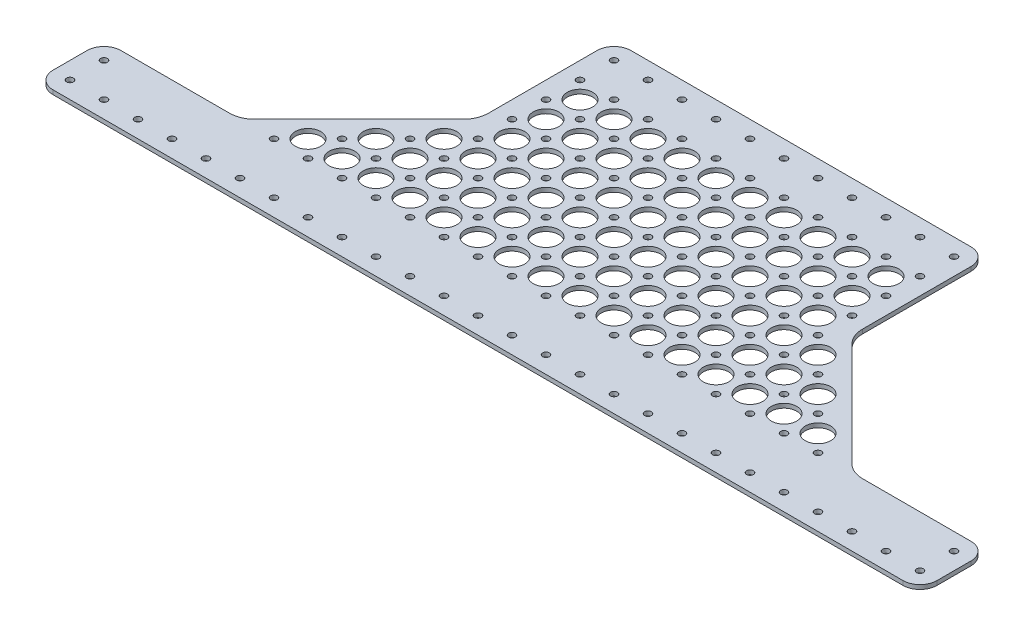
SolidWorks part; units mm, degrees
material "6061 Alloy"
ref_plane "Front Plane" through (0, 0, 0) normal (0, 0, 1) x (1, 0, 0)
ref_plane "Top Plane" through (0, 0, 0) normal (0, 1, 0) x (1, 0, 0)
ref_plane "Right Plane" through (0, 0, 0) normal (1, 0, 0) x (0, 0, -1)
sketch "Sketch1" plane through (0, 0, 0) normal (0, 1, 0) x (1, 0, 0)
  line L0 (0, 0) -> (0, 101.6)
  line L1 (0, 101.6) -> (279.4, 101.6)
  line L2 (279.4, 101.6) -> (279.4, 0)
  line L3 (279.4, 0) -> (368.3045, -88.9045)
  line L4 (368.3045, -88.9045) -> (469.9045, -88.9045)
  line L5 (469.9045, -88.9045) -> (469.9045, -419.1045)
  line L6 (469.9045, -419.1045) -> (368.3045, -419.1045)
  line L7 (368.3045, -419.1045) -> (279.4, -508.0091)
  line L8 (279.4, -508.0091) -> (279.4, -609.6091)
  line L9 (279.4, -609.6091) -> (0, -609.6091)
  line L10 (0, -609.6091) -> (0, -508.0091)
  line L11 (0, -508.0091) -> (-88.9045, -419.1045)
  line L12 (-88.9045, -419.1045) -> (-190.5045, -419.1045)
  line L13 (-190.5045, -419.1045) -> (-190.5045, -88.9045)
  line L14 (-190.5045, -88.9045) -> (-88.9045, -88.9045)
  line L15 (-88.9045, -88.9045) -> (0, 0)
  line L16 (-190.5045, -88.9045) -> (-177.8045, -88.9045)
  line L17 (-177.8045, -88.9045) -> (-177.8045, -419.1045) construction
  line L18 (-177.8045, -419.1045) -> (-190.5045, -419.1045)
  line L19 (-177.8045, -101.6045) -> (-177.8045, -127.0045) construction
  line L20 (139.7, -898.4) -> (139.7, 49101.6) construction
  line L21 (-966.4523, 88.9) -> (49033.5477, 88.9) construction
  line L22 (12.7, 88.9) -> (38.1, 88.9) construction
  line L23 (-1190.5045, -254.0045) -> (48809.4955, -254.0045) construction
  line L24 (-190.5045, -368.3045) -> (-88.9045, -368.3045) construction
  line L25 (-88.9045, -368.3045) -> (-88.9045, -419.1045) construction
  line L26 (-101.6045, -406.4045) -> (-127.0045, -406.4045) construction
  line L27 (-101.6045, -381.0045) -> (-127.0045, -381.0045) construction
  line L28 (-1102.5698, -114.3045) -> (48897.4302, -114.3045) construction
  line L29 (-1089.6596, -165.1045) -> (48910.3404, -165.1045) construction
  line L30 (-177.8045, -127.0045) -> (-152.4045, -127.0045) construction
  circle A0 centre (-177.8045, -101.6045) radius 2.54
  circle A1 centre (-177.8045, -127.0045) radius 2.54
  circle A2 centre (-177.8045, -152.4045) radius 2.54
  circle A3 centre (-177.8045, -177.8045) radius 2.54
  circle A4 centre (-177.8045, -203.2045) radius 2.54
  circle A5 centre (-177.8045, -228.6045) radius 2.54
  circle A6 centre (-177.8045, -254.0045) radius 2.54
  circle A7 centre (-177.8045, -279.4045) radius 2.54
  circle A8 centre (-177.8045, -304.8045) radius 2.54
  circle A9 centre (-177.8045, -330.2045) radius 2.54
  circle A10 centre (-177.8045, -355.6045) radius 2.54
  circle A11 centre (-177.8045, -381.0045) radius 2.54
  circle A12 centre (-177.8045, -406.4045) radius 2.54
  circle A13 centre (457.2045, -406.4045) radius 2.54
  circle A14 centre (457.2045, -381.0045) radius 2.54
  circle A15 centre (457.2045, -355.6045) radius 2.54
  circle A16 centre (457.2045, -330.2045) radius 2.54
  circle A17 centre (457.2045, -304.8045) radius 2.54
  circle A18 centre (457.2045, -279.4045) radius 2.54
  circle A19 centre (457.2045, -254.0045) radius 2.54
  circle A20 centre (457.2045, -228.6045) radius 2.54
  circle A21 centre (457.2045, -152.4045) radius 2.54
  circle A22 centre (457.2045, -177.8045) radius 2.54
  circle A23 centre (457.2045, -203.2045) radius 2.54
  circle A24 centre (457.2045, -127.0045) radius 2.54
  circle A25 centre (457.2045, -101.6045) radius 2.54
  circle A26 centre (12.7, 88.9) radius 2.54
  circle A27 centre (38.1, 88.9) radius 2.54
  circle A28 centre (63.5, 88.9) radius 2.54
  circle A29 centre (88.9, 88.9) radius 2.54
  circle A30 centre (114.3, 88.9) radius 2.54
  circle A31 centre (139.7, 88.9) radius 2.54
  circle A32 centre (165.1, 88.9) radius 2.54
  circle A33 centre (190.5, 88.9) radius 2.54
  circle A34 centre (215.9, 88.9) radius 2.54
  circle A35 centre (241.3, 88.9) radius 2.54
  circle A36 centre (266.7, 88.9) radius 2.54
  circle A37 centre (266.7, -596.9091) radius 2.54
  circle A38 centre (241.3, -596.9091) radius 2.54
  circle A39 centre (215.9, -596.9091) radius 2.54
  circle A40 centre (190.5, -596.9091) radius 2.54
  circle A41 centre (165.1, -596.9091) radius 2.54
  circle A42 centre (139.7, -596.9091) radius 2.54
  circle A43 centre (114.3, -596.9091) radius 2.54
  circle A44 centre (88.9, -596.9091) radius 2.54
  circle A45 centre (63.5, -596.9091) radius 2.54
  circle A46 centre (38.1, -596.9091) radius 2.54
  circle A47 centre (12.7, -596.9091) radius 2.54
  circle A48 centre (-101.6045, -381.0045) radius 2.54
  circle A49 centre (-101.6045, -406.4045) radius 2.54
  circle A50 centre (381.0045, -406.4045) radius 2.54
  circle A51 centre (381.0045, -381.0045) radius 2.54
  circle A52 centre (-127.0045, -406.4045) radius 2.54
  circle A53 centre (-152.4045, -406.4045) radius 2.54
  circle A54 centre (-127.0045, -381.0045) radius 2.54
  circle A55 centre (-152.4045, -381.0045) radius 2.54
  circle A56 centre (431.8045, -381.0045) radius 2.54
  circle A57 centre (406.4045, -381.0045) radius 2.54
  circle A58 centre (431.8045, -406.4045) radius 2.54
  circle A59 centre (406.4045, -406.4045) radius 2.54
  circle A60 centre (-152.4045, -127.0045) radius 2.54
  circle A61 centre (-152.4045, -152.4045) radius 2.54
  circle A62 centre (-127.0045, -127.0045) radius 2.54
  circle A63 centre (-127.0045, -152.4045) radius 2.54
  circle A64 centre (-101.6045, -127.0045) radius 2.54
  circle A65 centre (-101.6045, -152.4045) radius 2.54
  circle A66 centre (-76.2045, -127.0045) radius 2.54
  circle A67 centre (-76.2045, -152.4045) radius 2.54
  circle A68 centre (-50.8045, -127.0045) radius 2.54
  circle A69 centre (-50.8045, -152.4045) radius 2.54
  circle A70 centre (-25.4045, -127.0045) radius 2.54
  circle A71 centre (-25.4045, -152.4045) radius 2.54
  circle A72 centre (-0.0045, -127.0045) radius 2.54
  circle A73 centre (-0.0045, -152.4045) radius 2.54
  circle A74 centre (25.3955, -127.0045) radius 2.54
  circle A75 centre (25.3955, -152.4045) radius 2.54
  circle A76 centre (50.7955, -127.0045) radius 2.54
  circle A77 centre (50.7955, -152.4045) radius 2.54
  circle A78 centre (76.1955, -127.0045) radius 2.54
  circle A79 centre (76.1955, -152.4045) radius 2.54
  circle A80 centre (101.5955, -127.0045) radius 2.54
  circle A81 centre (101.5955, -152.4045) radius 2.54
  circle A82 centre (126.9955, -127.0045) radius 2.54
  circle A83 centre (126.9955, -152.4045) radius 2.54
  circle A84 centre (152.3955, -127.0045) radius 2.54
  circle A85 centre (152.3955, -152.4045) radius 2.54
  circle A86 centre (177.7955, -127.0045) radius 2.54
  circle A87 centre (177.7955, -152.4045) radius 2.54
  circle A88 centre (203.1955, -127.0045) radius 2.54
  circle A89 centre (203.1955, -152.4045) radius 2.54
  circle A90 centre (228.5955, -127.0045) radius 2.54
  circle A91 centre (228.5955, -152.4045) radius 2.54
  circle A92 centre (253.9955, -127.0045) radius 2.54
  circle A93 centre (253.9955, -152.4045) radius 2.54
  circle A94 centre (279.3955, -127.0045) radius 2.54
  circle A95 centre (279.3955, -152.4045) radius 2.54
  circle A96 centre (304.7955, -127.0045) radius 2.54
  circle A97 centre (304.7955, -152.4045) radius 2.54
  circle A98 centre (330.1955, -127.0045) radius 2.54
  circle A99 centre (330.1955, -152.4045) radius 2.54
  circle A100 centre (355.5955, -127.0045) radius 2.54
  circle A101 centre (355.5955, -152.4045) radius 2.54
  circle A102 centre (380.9955, -127.0045) radius 2.54
  circle A103 centre (380.9955, -152.4045) radius 2.54
  circle A104 centre (406.3955, -127.0045) radius 2.54
  circle A105 centre (406.3955, -152.4045) radius 2.54
  circle A106 centre (431.7955, -127.0045) radius 2.54
  circle A107 centre (431.7955, -152.4045) radius 2.54
  point P50 (139.7, 101.6)
  point P105 (-190.5045, -254.0045)
  dimension "D11" = 5.08
  dimension "D16" = 5.08
  dimension "D21" = 5.08
  dimension "D22" = 5.08
  dimension "D1" = 135
  dimension "D2" = 135
  dimension "D3" = 135
  dimension "D4" = 135
  dimension "D5" = 101.6
  dimension "D6" = 279.4
  dimension "D7" = 330.2
  dimension "D8" = 101.6
  dimension "D9" = 125.73
  dimension "D10" = 12.7
  dimension "D12" = 12.7
  dimension "D13" = 25.4
  dimension "D15" = 12.7
  dimension "D17" = 12.7
  dimension "D18" = 25.4
  dimension "D19" = 101.6
  dimension "D20" = 50.8
  dimension "D23" = 12.7
  dimension "D24" = 12.7
  dimension "D25" = 12.7
  dimension "D26" = 12.7
  dimension "D27" = 25.4
  dimension "D28" = 25.4
  dimension "D29" = 25.4
  dimension "D30" = 50.8
  dimension "D31" = 25.4
  dimension "D14" = 13
extrude "Boss-Extrude1" add sketch "Sketch1" along normal blind 3.175 contours L15 L14 L13 L12 L11 L10 L9 L8 L7 L6 L5 L4 L3 L2 L1 L0 A107 A106 A105 A104 A103 A102 A101 A100 A99 A98 A97 A96 A95 A94 A93 A92 region at (139.7, 0, 254.2329)
sketch "Sketch2" plane through (0, 0, 609.6091) normal (0, 0, 1) x (1, 0, 0)
  line L0 (279.4, 0) -> (0, 0) construction
  line L1 (-203.0133, -12.7) -> (508.1867, -12.7)
  line L2 (-203.0133, -12.7) -> (-203.0133, 12.7)
  line L3 (-203.0133, 12.7) -> (508.1867, 12.7)
  line L4 (508.1867, -12.7) -> (508.1867, 12.7)
  line L5 (-203.0133, -12.7) -> (508.1867, 12.7) construction
  line L6 (-203.0133, 12.7) -> (508.1867, -12.7) construction
  point P0 (152.5867, 0)
  dimension "D1" = 711.2
  dimension "D2" = 25.4
extrude "Cut-Extrude2" cut sketch "Sketch2" against normal blind 469.9
sketch "Sketch3" plane through (0, 3.175, 0) normal (0, 1, 0) x (1, 0, 0)
  line L0 (12.7, 88.9) -> (38.1, 88.9) construction
  line L1 (12.7, 88.9) -> (12.7, 63.5) construction
  line L2 (0, 0) -> (0, 101.6) construction
  line L3 (12.7, -88.9) -> (-12.7, -88.9) construction
  line L4 (12.7, -63.5) -> (-12.7, -63.5) construction
  line L5 (12.7, -38.1) -> (-12.7, -38.1) construction
  line L6 (0, 101.6) -> (279.4, 101.6) construction
  line L7 (266.7, -88.9) -> (292.1, -88.9) construction
  line L8 (266.7, -63.5) -> (292.1, -63.5) construction
  line L9 (266.7, -38.1) -> (292.1, -38.1) construction
  line L10 (25.4, 50.8) -> (50.8, 50.8) construction
  line L11 (25.4, 50.8) -> (25.4, 25.4) construction
  line L12 (279.4, 101.6) -> (279.4, 0) construction
  line L13 (25.4, -25.4) -> (0, -25.4) construction
  circle A0 centre (12.7, 88.9) radius 2.54
  circle A1 centre (38.1, 88.9) radius 2.54
  circle A2 centre (63.5, 88.9) radius 2.54
  circle A3 centre (88.9, 88.9) radius 2.54
  circle A4 centre (114.3, 88.9) radius 2.54
  circle A5 centre (139.7, 88.9) radius 2.54
  circle A6 centre (165.1, 88.9) radius 2.54
  circle A7 centre (190.5, 88.9) radius 2.54
  circle A8 centre (215.9, 88.9) radius 2.54
  circle A9 centre (241.3, 88.9) radius 2.54
  circle A10 centre (266.7, 88.9) radius 2.54
  circle A18 centre (12.7, 63.5) radius 2.54
  circle A19 centre (38.1, 63.5) radius 2.54
  circle A20 centre (63.5, 63.5) radius 2.54
  circle A21 centre (88.9, 63.5) radius 2.54
  circle A22 centre (114.3, 63.5) radius 2.54
  circle A23 centre (139.7, 63.5) radius 2.54
  circle A24 centre (165.1, 63.5) radius 2.54
  circle A25 centre (190.5, 63.5) radius 2.54
  circle A26 centre (215.9, 63.5) radius 2.54
  circle A27 centre (241.3, 63.5) radius 2.54
  circle A28 centre (266.7, 63.5) radius 2.54
  circle A36 centre (12.7, 38.1) radius 2.54
  circle A37 centre (38.1, 38.1) radius 2.54
  circle A38 centre (63.5, 38.1) radius 2.54
  circle A39 centre (88.9, 38.1) radius 2.54
  circle A40 centre (114.3, 38.1) radius 2.54
  circle A41 centre (139.7, 38.1) radius 2.54
  circle A42 centre (165.1, 38.1) radius 2.54
  circle A43 centre (190.5, 38.1) radius 2.54
  circle A44 centre (215.9, 38.1) radius 2.54
  circle A45 centre (241.3, 38.1) radius 2.54
  circle A46 centre (266.7, 38.1) radius 2.54
  circle A54 centre (12.7, 12.7) radius 2.54
  circle A55 centre (38.1, 12.7) radius 2.54
  circle A56 centre (63.5, 12.7) radius 2.54
  circle A57 centre (88.9, 12.7) radius 2.54
  circle A58 centre (114.3, 12.7) radius 2.54
  circle A59 centre (139.7, 12.7) radius 2.54
  circle A60 centre (165.1, 12.7) radius 2.54
  circle A61 centre (190.5, 12.7) radius 2.54
  circle A62 centre (215.9, 12.7) radius 2.54
  circle A63 centre (241.3, 12.7) radius 2.54
  circle A64 centre (266.7, 12.7) radius 2.54
  circle A72 centre (12.7, -12.7) radius 2.54
  circle A73 centre (38.1, -12.7) radius 2.54
  circle A74 centre (63.5, -12.7) radius 2.54
  circle A75 centre (88.9, -12.7) radius 2.54
  circle A76 centre (114.3, -12.7) radius 2.54
  circle A77 centre (139.7, -12.7) radius 2.54
  circle A78 centre (165.1, -12.7) radius 2.54
  circle A79 centre (190.5, -12.7) radius 2.54
  circle A80 centre (215.9, -12.7) radius 2.54
  circle A81 centre (241.3, -12.7) radius 2.54
  circle A82 centre (266.7, -12.7) radius 2.54
  circle A90 centre (12.7, -38.1) radius 2.54
  circle A91 centre (38.1, -38.1) radius 2.54
  circle A92 centre (63.5, -38.1) radius 2.54
  circle A93 centre (88.9, -38.1) radius 2.54
  circle A94 centre (114.3, -38.1) radius 2.54
  circle A95 centre (139.7, -38.1) radius 2.54
  circle A96 centre (165.1, -38.1) radius 2.54
  circle A97 centre (190.5, -38.1) radius 2.54
  circle A98 centre (215.9, -38.1) radius 2.54
  circle A99 centre (241.3, -38.1) radius 2.54
  circle A100 centre (266.7, -38.1) radius 2.54
  circle A108 centre (12.7, -63.5) radius 2.54
  circle A109 centre (38.1, -63.5) radius 2.54
  circle A110 centre (63.5, -63.5) radius 2.54
  circle A111 centre (88.9, -63.5) radius 2.54
  circle A112 centre (114.3, -63.5) radius 2.54
  circle A113 centre (139.7, -63.5) radius 2.54
  circle A114 centre (165.1, -63.5) radius 2.54
  circle A115 centre (190.5, -63.5) radius 2.54
  circle A116 centre (215.9, -63.5) radius 2.54
  circle A117 centre (241.3, -63.5) radius 2.54
  circle A118 centre (266.7, -63.5) radius 2.54
  circle A126 centre (12.7, -88.9) radius 2.54
  circle A127 centre (38.1, -88.9) radius 2.54
  circle A128 centre (63.5, -88.9) radius 2.54
  circle A129 centre (88.9, -88.9) radius 2.54
  circle A130 centre (114.3, -88.9) radius 2.54
  circle A131 centre (139.7, -88.9) radius 2.54
  circle A132 centre (165.1, -88.9) radius 2.54
  circle A133 centre (190.5, -88.9) radius 2.54
  circle A134 centre (215.9, -88.9) radius 2.54
  circle A135 centre (241.3, -88.9) radius 2.54
  circle A136 centre (266.7, -88.9) radius 2.54
  circle A211 centre (-12.7, -88.9) radius 2.54
  circle A212 centre (-38.1, -88.9) radius 2.54
  circle A213 centre (-63.5, -88.9) radius 2.54
  circle A214 centre (-12.7, -63.5) radius 2.54
  circle A215 centre (-38.1, -63.5) radius 2.54
  circle A216 centre (-12.7, -38.1) radius 2.54
  circle A224 centre (292.1, -88.9) radius 2.54
  circle A225 centre (317.5, -88.9) radius 2.54
  circle A226 centre (342.9, -88.9) radius 2.54
  circle A227 centre (292.1, -63.5) radius 2.54
  circle A228 centre (317.5, -63.5) radius 2.54
  circle A229 centre (292.1, -38.1) radius 2.54
  circle A230 centre (25.4, 50.8) radius 9.525
  circle A231 centre (50.8, 50.8) radius 9.525
  circle A232 centre (292.1, 88.9) radius 2.54 [skipped]
  circle A233 centre (317.5, 88.9) radius 2.54 [skipped]
  circle A234 centre (342.9, 88.9) radius 2.54 [skipped]
  circle A235 centre (368.3, 88.9) radius 2.54 [skipped]
  circle A236 centre (393.7, 88.9) radius 2.54 [skipped]
  circle A237 centre (419.1, 88.9) radius 2.54 [skipped]
  circle A238 centre (444.5, 88.9) radius 2.54 [skipped]
  circle A239 centre (12.7, -114.3) radius 2.54 [skipped]
  circle A240 centre (38.1, -114.3) radius 2.54 [skipped]
  circle A241 centre (63.5, -114.3) radius 2.54 [skipped]
  circle A242 centre (88.9, -114.3) radius 2.54 [skipped]
  circle A243 centre (114.3, -114.3) radius 2.54 [skipped]
  circle A244 centre (139.7, -114.3) radius 2.54 [skipped]
  circle A245 centre (165.1, -114.3) radius 2.54 [skipped]
  circle A246 centre (190.5, -114.3) radius 2.54 [skipped]
  circle A247 centre (215.9, -114.3) radius 2.54 [skipped]
  circle A248 centre (241.3, -114.3) radius 2.54 [skipped]
  circle A249 centre (266.7, -114.3) radius 2.54 [skipped]
  circle A250 centre (76.2, 50.8) radius 9.525
  circle A251 centre (101.6, 50.8) radius 9.525
  circle A252 centre (127, 50.8) radius 9.525
  circle A253 centre (152.4, 50.8) radius 9.525
  circle A254 centre (177.8, 50.8) radius 9.525
  circle A255 centre (203.2, 50.8) radius 9.525
  circle A256 centre (228.6, 50.8) radius 9.525
  circle A257 centre (254, 50.8) radius 9.525
  circle A265 centre (50.8, 25.4) radius 9.525
  circle A266 centre (76.2, 25.4) radius 9.525
  circle A267 centre (101.6, 25.4) radius 9.525
  circle A268 centre (127, 25.4) radius 9.525
  circle A269 centre (152.4, 25.4) radius 9.525
  circle A270 centre (177.8, 25.4) radius 9.525
  circle A271 centre (203.2, 25.4) radius 9.525
  circle A272 centre (228.6, 25.4) radius 9.525
  circle A273 centre (254, 25.4) radius 9.525
  circle A281 centre (50.8, 0) radius 9.525
  circle A282 centre (76.2, 0) radius 9.525
  circle A283 centre (101.6, 0) radius 9.525
  circle A284 centre (127, 0) radius 9.525
  circle A285 centre (152.4, 0) radius 9.525
  circle A286 centre (177.8, 0) radius 9.525
  circle A287 centre (203.2, 0) radius 9.525
  circle A288 centre (228.6, 0) radius 9.525
  circle A289 centre (254, 0) radius 9.525
  circle A297 centre (50.8, -25.4) radius 9.525
  circle A298 centre (76.2, -25.4) radius 9.525
  circle A299 centre (101.6, -25.4) radius 9.525
  circle A300 centre (127, -25.4) radius 9.525
  circle A301 centre (152.4, -25.4) radius 9.525
  circle A302 centre (177.8, -25.4) radius 9.525
  circle A303 centre (203.2, -25.4) radius 9.525
  circle A304 centre (228.6, -25.4) radius 9.525
  circle A305 centre (254, -25.4) radius 9.525
  circle A306 centre (279.4, -25.4) radius 9.525
  circle A313 centre (50.8, -50.8) radius 9.525
  circle A314 centre (76.2, -50.8) radius 9.525
  circle A315 centre (101.6, -50.8) radius 9.525
  circle A316 centre (127, -50.8) radius 9.525
  circle A317 centre (152.4, -50.8) radius 9.525
  circle A318 centre (177.8, -50.8) radius 9.525
  circle A319 centre (203.2, -50.8) radius 9.525
  circle A320 centre (228.6, -50.8) radius 9.525
  circle A321 centre (254, -50.8) radius 9.525
  circle A322 centre (279.4, -50.8) radius 9.525
  circle A323 centre (304.8, -50.8) radius 9.525
  circle A329 centre (50.8, -76.2) radius 9.525
  circle A330 centre (76.2, -76.2) radius 9.525
  circle A331 centre (101.6, -76.2) radius 9.525
  circle A332 centre (127, -76.2) radius 9.525
  circle A333 centre (152.4, -76.2) radius 9.525
  circle A334 centre (177.8, -76.2) radius 9.525
  circle A335 centre (203.2, -76.2) radius 9.525
  circle A336 centre (228.6, -76.2) radius 9.525
  circle A337 centre (254, -76.2) radius 9.525
  circle A338 centre (279.4, -76.2) radius 9.525
  circle A339 centre (304.8, -76.2) radius 9.525
  circle A340 centre (330.2, -76.2) radius 9.525
  circle A345 centre (25.4, 25.4) radius 9.525
  circle A346 centre (25.4, 0) radius 9.525
  circle A347 centre (25.4, -25.4) radius 9.525
  circle A348 centre (25.4, -50.8) radius 9.525
  circle A349 centre (25.4, -76.2) radius 9.525
  circle A350 centre (279.4, 25.4) radius 9.525 [skipped]
  circle A351 centre (304.8, 25.4) radius 9.525 [skipped]
  circle A352 centre (330.2, 25.4) radius 9.525 [skipped]
  circle A353 centre (355.6, 25.4) radius 9.525 [skipped]
  circle A354 centre (381, 25.4) radius 9.525 [skipped]
  circle A355 centre (406.4, 25.4) radius 9.525 [skipped]
  circle A356 centre (431.8, 25.4) radius 9.525 [skipped]
  circle A357 centre (279.4, 0) radius 9.525 [skipped]
  circle A358 centre (304.8, 0) radius 9.525 [skipped]
  circle A359 centre (330.2, 0) radius 9.525 [skipped]
  circle A360 centre (355.6, 0) radius 9.525 [skipped]
  circle A361 centre (381, 0) radius 9.525 [skipped]
  circle A362 centre (406.4, 0) radius 9.525 [skipped]
  circle A363 centre (431.8, 0) radius 9.525 [skipped]
  circle A364 centre (304.8, 50.8) radius 9.525 [skipped]
  circle A365 centre (330.2, 50.8) radius 9.525 [skipped]
  circle A366 centre (355.6, 50.8) radius 9.525 [skipped]
  circle A367 centre (381, 50.8) radius 9.525 [skipped]
  circle A368 centre (406.4, 50.8) radius 9.525 [skipped]
  circle A369 centre (431.8, 50.8) radius 9.525 [skipped]
  circle A370 centre (279.4, 50.8) radius 9.525 [skipped]
  circle A371 centre (330.2, -25.4) radius 9.525 [skipped]
  circle A372 centre (355.6, -25.4) radius 9.525 [skipped]
  circle A373 centre (381, -25.4) radius 9.525 [skipped]
  circle A374 centre (406.4, -25.4) radius 9.525 [skipped]
  circle A375 centre (431.8, -25.4) radius 9.525 [skipped]
  circle A376 centre (381, -50.8) radius 9.525 [skipped]
  circle A377 centre (406.4, -50.8) radius 9.525 [skipped]
  circle A378 centre (431.8, -50.8) radius 9.525 [skipped]
  circle A379 centre (406.4, -76.2) radius 9.525 [skipped]
  circle A380 centre (431.8, -76.2) radius 9.525 [skipped]
  circle A381 centre (381, -76.2) radius 9.525 [skipped]
  circle A382 centre (355.6, -76.2) radius 9.525 [skipped]
  circle A383 centre (355.6, -50.8) radius 9.525 [skipped]
  circle A384 centre (330.2, -50.8) radius 9.525 [skipped]
  circle A385 centre (304.8, -25.4) radius 9.525 [skipped]
  circle A386 centre (0, -25.4) radius 9.525
  circle A387 centre (0, -50.8) radius 9.525
  circle A388 centre (0, -76.2) radius 9.525
  circle A390 centre (-25.4, -50.8) radius 9.525
  circle A391 centre (-25.4, -76.2) radius 9.525
  circle A394 centre (-50.8, -76.2) radius 9.525
  circle A395 centre (-50.8, -25.4) radius 9.525 [skipped]
  circle A396 centre (-50.8, -50.8) radius 9.525 [skipped]
  circle A397 centre (-25.4, -25.4) radius 9.525 [skipped]
  dimension "D1" = 5.08
  dimension "D6" = 19.05
  dimension "D2" = 25.4
  dimension "D4" = 25.4
  dimension "D7" = 25.4
  dimension "D8" = 25.4
  dimension "D9" = 25.4
  dimension "D10" = 25.4
  dimension "D11" = 25.4
  dimension "D12" = 25.4
  dimension "D13" = 25.4
  dimension "D14" = 50.8
  dimension "D16" = 25.4
  dimension "D17" = 25.4
  dimension "D19" = 25.4
  dimension "D20" = 25.4
  dimension "D3" = 18
  dimension "D5" = 9
  dimension "D18" = 17
  dimension "D15" = 6
  dimension "D21" = 4
extrude "Cut-Extrude3" cut sketch "Sketch3" against normal blind 3.175
fillet "Fillet1" radius 12.7 6 edges at (-190.5045, 1.5875, 88.9045) (-190.5045, 1.5875, 139.7091) (469.9045, 1.5875, 88.9045) (469.9045, 1.5875, 139.7091) (279.4, 1.5875, -101.6) (0, 1.5875, -101.6)
fillet "Fillet2" radius 19.05 4 edges at (368.3045, 1.5875, 88.9045) (279.4, 1.5875, 0) (-88.9045, 1.5875, 88.9045) (0, 1.5875, 0)
sketch "Sketch4" plane through (0, 0, 0) normal (0, -1, 0) x (1, 0, 0)
  line L0 (-1189.9314, 139.7091) -> (48810.0686, 139.7091) construction
  line L1 (-190.5045, -850.8511) -> (-190.5045, 49149.1489) construction
  line L4 (457.2045, 139.7091) -> (-177.8045, 139.7091) construction
  line L5 (-190.5045, 127.0091) -> (-190.5045, 101.6045) construction
  point P3 (-190.5045, 139.7091)
